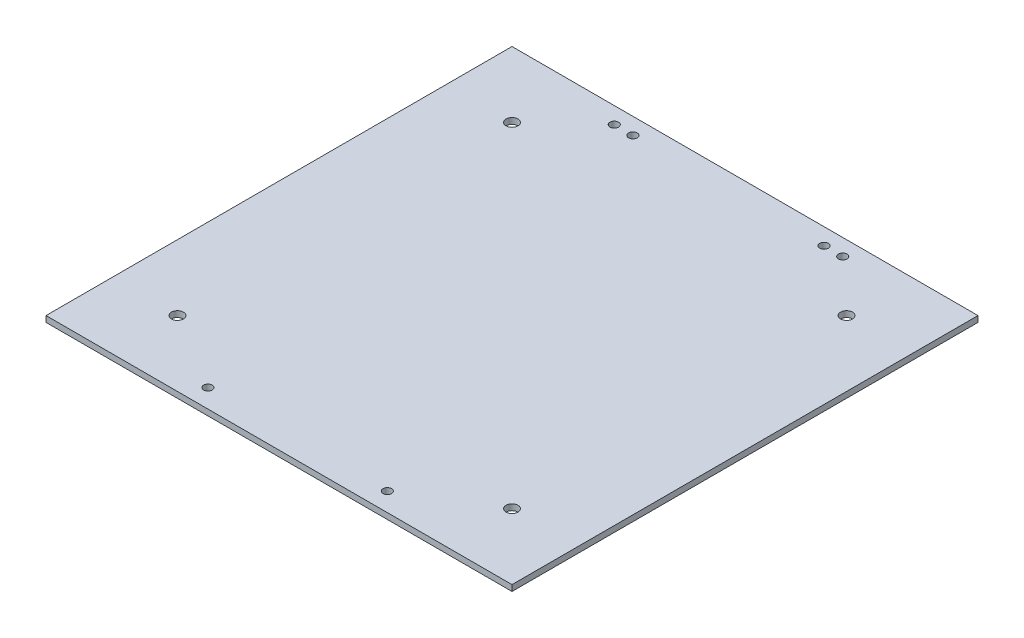
SolidWorks part; units mm, degrees
ref_plane "Front Plane" through (0, 0, 0) normal (0, 0, 1) x (1, 0, 0)
ref_plane "Top Plane" through (0, 0, 0) normal (0, 1, 0) x (1, 0, 0)
ref_plane "Right Plane" through (0, 0, 0) normal (1, 0, 0) x (0, 0, -1)
sketch "Sketch1" plane through (0, 0, 0) normal (0, 1, 0) x (1, 0, 0)
  line L1 (0, 0) -> (247.65, 0)
  line L2 (0, 0) -> (0, 247.65)
  line L3 (0, 247.65) -> (247.65, 247.65)
  line L4 (247.65, 0) -> (247.65, 247.65)
  dimension "D1" = 247.65
  dimension "D2" = 247.65
extrude "Boss-Extrude1" add sketch "Sketch1" along normal blind 3.175
sketch "Sketch2" plane through (0, 3.175, 0) normal (0, 1, 0) x (1, 0, 0)
  line L0 (65.405, 238.8616) -> (70.739, 238.8616) construction
  line L1 (176.911, 238.8616) -> (182.245, 238.8616) construction
  line L2 (247.65, 247.65) -> (0, 247.65) construction
  line L3 (0, 0) -> (247.65, 0) construction
  line L4 (0, 247.65) -> (0, 0) construction
  line L5 (247.65, 0) -> (247.65, 247.65) construction
  circle A0 centre (63.119, 238.8616) radius 2.286
  circle A1 centre (73.025, 238.8616) radius 2.286
  circle A2 centre (174.625, 238.8616) radius 2.286
  circle A3 centre (184.531, 238.8616) radius 2.286
  circle A4 centre (76.1568, 9.906) radius 2.286
  circle A5 centre (171.4932, 9.906) radius 2.286
  point P14 (123.825, 247.65)
  point P19 (0, 0)
  point P20 (0, 0)
  dimension "D3" = 4.572
  dimension "D7" = 4.572
  dimension "D10" = 76.1568
  dimension "D1" = 5.334
  dimension "D2" = 5.334
  dimension "D4" = 8.7884
  dimension "D5" = 50.8
  dimension "D6" = 50.8
  dimension "D8" = 9.906
  dimension "D9" = 76.1568
extrude "Cut-Extrude1" cut sketch "Sketch2" against normal through all
sketch "Sketch3" plane through (0, 3.175, 0) normal (0, 1, 0) x (1, 0, 0)
  line L0 (247.65, 0) -> (0, 247.65) construction
  line L1 (247.65, 247.65) -> (0, 247.65) construction
  line L2 (247.65, 0) -> (247.65, 247.65) construction
  circle A0 centre (212.725, 212.725) radius 3.175
  circle A1 centre (212.725, 34.925) radius 3.175
  circle A2 centre (34.925, 34.925) radius 3.175
  circle A3 centre (34.925, 212.725) radius 3.175
  point P10 (123.825, 123.825)
  dimension "D1" = 6.35
  dimension "D2" = 34.925
  dimension "D3" = 34.925
  dimension "D5" = 177.8
  dimension "D6" = 125.7236
  dimension "D4" = 4
extrude "Cut-Extrude2" cut sketch "Sketch3" against normal through all
